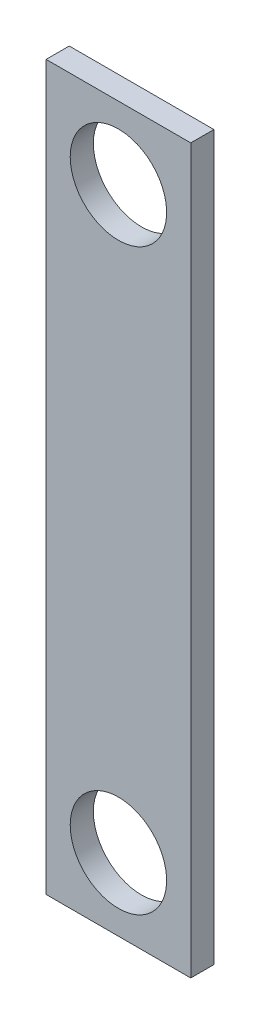
SolidWorks part; units mm, degrees
ref_plane "Front Plane" through (0, 0, 0) normal (0, 0, 1) x (1, 0, 0)
ref_plane "Top Plane" through (0, 0, 0) normal (0, 1, 0) x (1, 0, 0)
ref_plane "Right Plane" through (0, 0, 0) normal (1, 0, 0) x (0, 0, -1)
sketch "Sketch1" plane through (0, 0, 0) normal (0, 0, 1) x (1, 0, 0)
  line L0 (0, 0) -> (0, -76.2) construction
  line L1 (0, -38.1) -> (-9.525, -38.1) construction
  line L2 (-9.525, -85.725) -> (9.525, -85.725)
  line L3 (-9.525, -85.725) -> (-9.525, 9.525)
  line L4 (-9.525, 9.525) -> (9.525, 9.525)
  line L5 (9.525, -85.725) -> (9.525, 9.525)
  line L6 (-9.525, -85.725) -> (9.525, 9.525) construction
  line L7 (-9.525, 9.525) -> (9.525, -85.725) construction
  circle A0 centre (0, 0) radius 3.9688 construction
  circle A1 centre (0, -38.1) radius 3.175 construction
  circle A2 centre (0, 0) radius 6.35
  circle A3 centre (0, -76.2) radius 3.9687 construction
  circle A4 centre (0, -76.2) radius 6.35
  dimension "D1" = 7.9375
  dimension "D2" = 6.35
  dimension "D3" = 38.1
  dimension "D6" = 12.7
  dimension "D4" = 19.05
  dimension "D5" = 95.25
extrude "Boss-Extrude2" add sketch "Sketch1" along normal blind 3.048
